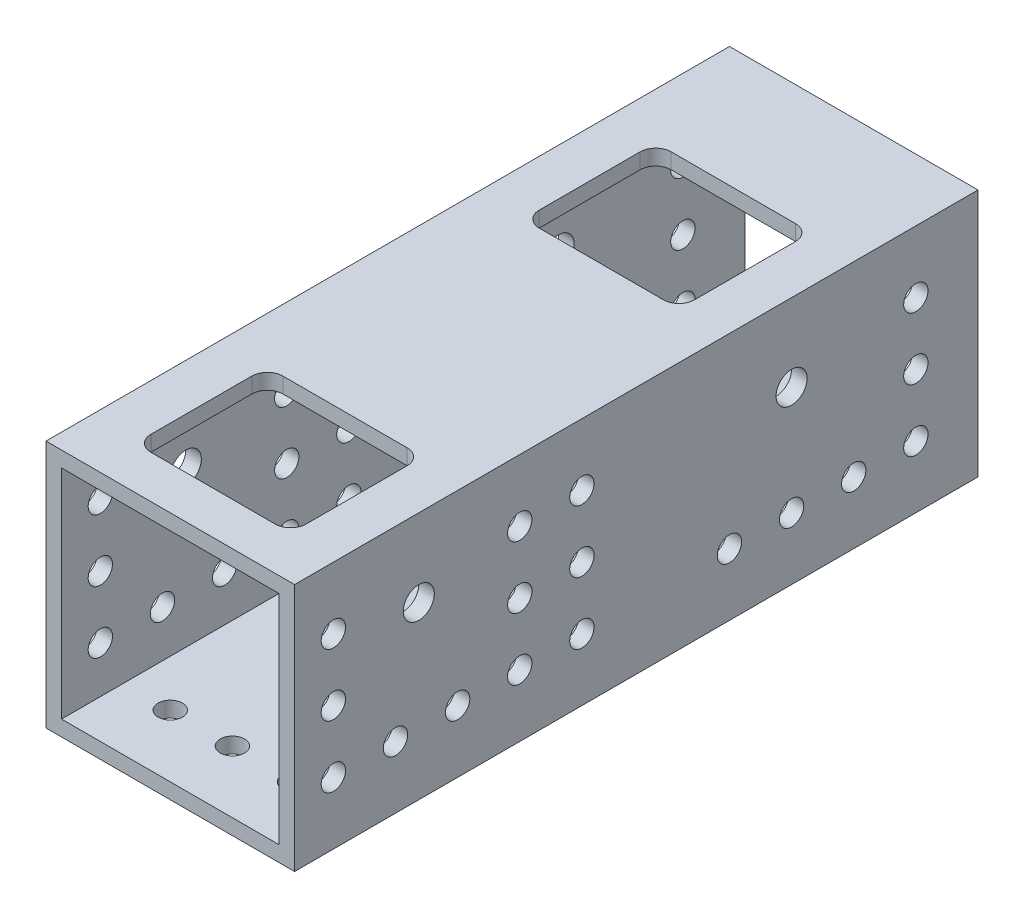
SolidWorks part; units mm, degrees
material "6061-T6 (SS)"
ref_plane "Front Plane" through (0, 0, 0) normal (0, 0, 1) x (1, 0, 0)
ref_plane "Top Plane" through (0, 0, 0) normal (0, 1, 0) x (1, 0, 0)
ref_plane "Right Plane" through (0, 0, 0) normal (1, 0, 0) x (0, 0, -1)
sketch "Sketch1" plane through (0, 0, 0) normal (0, 0, 1) x (1, 0, 0)
  line L1 (-25.4, -25.4) -> (25.4, -25.4)
  line L2 (-25.4, -25.4) -> (-25.4, 25.4)
  line L3 (-25.4, 25.4) -> (25.4, 25.4)
  line L4 (25.4, -25.4) -> (25.4, 25.4)
  line L5 (-25.4, -25.4) -> (25.4, 25.4) construction
  line L6 (-25.4, 25.4) -> (25.4, -25.4) construction
  point P0 (0, 0)
  dimension "D1" = 50.8
  dimension "D2" = 50.8
extrude "Boss-Extrude1" add sketch "Sketch1" along normal mid plane 139.7
shell "Shell1" thickness 3.175 removed face at (0, 0, -69.85) removed face at (0, 0, 69.85)
sketch "Sketch2" plane through (0, 0, 0) normal (0, 1, 0) x (1, 0, 0)
  line L0 (25.4, 69.85) -> (-25.4, 69.85) construction
  line L1 (15.875, 45.2437) -> (-15.875, 45.2437)
  line L2 (15.875, 45.2437) -> (15.875, 18.2563)
  line L3 (15.875, 18.2563) -> (-15.875, 18.2563)
  line L4 (-15.875, 45.2437) -> (-15.875, 18.2563)
  line L5 (25.4, -69.85) -> (-25.4, -69.85) construction
  line L7 (15.875, -34.1313) -> (-15.875, -34.1313)
  line L8 (15.875, -34.1313) -> (15.875, -61.1187)
  line L9 (15.875, -61.1187) -> (-15.875, -61.1187)
  line L10 (-15.875, -34.1313) -> (-15.875, -61.1187)
  point P4 (0, 45.2437)
  point P7 (0, 69.85)
  point P9 (15.875, 31.75)
  point P15 (0, -69.85)
  point P16 (0, -61.1187)
  point P17 (-15.875, -47.625)
  dimension "D1" = 31.75
  dimension "D2" = 26.9875
  dimension "D3" = 101.6
  dimension "D4" = 22.225
extrude "Cut-Extrude1" cut sketch "Sketch2" along normal through all
fillet "Fillet1" radius 3.175 4 edges at (15.875, 23.8125, -45.2437) (-15.875, 23.8125, -45.2437) (-15.875, 23.8125, -18.2563) (15.875, 23.8125, -18.2563)
sketch "Sketch3" plane through (0, 0, 0) normal (1, 0, 0) x (0, 0, -1)
  line L1 (-69.85, 25.4) -> (-69.85, -25.4) construction
  line L2 (-69.85, 25.4) -> (69.85, 25.4) construction
  circle A0 centre (31.75, 9.525) radius 3.175
  circle A1 centre (-44.45, 9.525) radius 3.175
  dimension "D1" = 6.35
  dimension "D2" = 25.4
  dimension "D3" = 76.2
  dimension "D4" = 15.875
extrude "Cut-Extrude2" cut sketch "Sketch3" against normal through all both and the other way through all
sketch "Sketch4" plane through (0, 0, 0) normal (1, 0, 0) x (0, 0, -1)
  line L0 (-69.85, 25.4) -> (69.85, 25.4) construction
  line L1 (69.85, 25.4) -> (69.85, -25.4) construction
  line L2 (-69.85, 25.4) -> (-69.85, -25.4) construction
  circle A0 centre (57.15, 12.7) radius 2.4892
  circle A1 centre (44.45, 12.7) radius 2.4892 construction
  circle A2 centre (31.75, 12.7) radius 2.4892 construction
  circle A3 centre (19.05, 12.7) radius 2.4892 construction
  circle A10 centre (44.45, 0) radius 2.4892 construction
  circle A11 centre (31.75, 0) radius 2.4892 construction
  circle A12 centre (19.05, 0) radius 2.4892 construction
  circle A19 centre (44.45, -12.7) radius 2.4892
  circle A20 centre (31.75, -12.7) radius 2.4892
  circle A21 centre (19.05, -12.7) radius 2.4892
  circle A28 centre (57.15, 0) radius 2.4892
  circle A29 centre (57.15, -12.7) radius 2.4892
  circle A30 centre (-61.9125, 12.7) radius 2.4892
  circle A31 centre (-49.2125, 12.7) radius 2.4892 construction
  circle A32 centre (-36.5125, 12.7) radius 2.4892 construction
  circle A33 centre (-23.8125, 12.7) radius 2.4892
  circle A34 centre (-11.1125, 12.7) radius 2.4892
  circle A35 centre (1.5875, 12.7) radius 2.4892 construction
  circle A36 centre (-49.2125, 0) radius 2.4892 construction
  circle A37 centre (-36.5125, 0) radius 2.4892 construction
  circle A38 centre (-23.8125, 0) radius 2.4892
  circle A39 centre (-11.1125, 0) radius 2.4892
  circle A40 centre (1.5875, 0) radius 2.4892 construction
  circle A41 centre (-49.2125, -12.7) radius 2.4892
  circle A42 centre (-36.5125, -12.7) radius 2.4892
  circle A43 centre (-23.8125, -12.7) radius 2.4892
  circle A44 centre (-11.1125, -12.7) radius 2.4892
  circle A45 centre (1.5875, -12.7) radius 2.4892 construction
  circle A46 centre (-61.9125, 0) radius 2.4892
  circle A47 centre (-61.9125, -12.7) radius 2.4892
  dimension "D1" = 4.9784
  dimension "D3" = 12.7
  dimension "D8" = 4.9784
  dimension "D9" = 7.9375
  dimension "D14" = 12.7
  dimension "D2" = 12.7
  dimension "D6" = 12.7
  dimension "D7" = 12.7
  dimension "D10" = 12.7
  dimension "D13" = 12.7
  dimension "D4" = 4
  dimension "D5" = 3
  dimension "D11" = 6
  dimension "D12" = 3
extrude "Cut-Extrude3" cut sketch "Sketch4" against normal through all both and the other way through all
sketch "Sketch5" plane through (0, 0, 0) normal (0, 1, 0) x (1, 0, 0)
  line L1 (25.4, -69.85) -> (-25.4, -69.85) construction
  line L2 (-25.4, -69.85) -> (-25.4, 69.85) construction
  circle A0 centre (-12.7, -57.15) radius 2.4892
  circle A1 centre (0, -57.15) radius 2.4892
  circle A2 centre (12.7, -57.15) radius 2.4892
  dimension "D1" = 4.9784
  dimension "D3" = 12.7
  dimension "D2" = 12.7
  dimension "D5" = 12.7
  dimension "D4" = 3
extrude "Cut-Extrude4" cut sketch "Sketch5" against normal through all and the other way through all
fillet "Fillet2" radius 3.175 4 edges at (-15.875, 23.8125, 34.1313) (-15.875, 23.8125, 61.1187) (15.875, 23.8125, 61.1187) (15.875, 23.8125, 34.1313)
